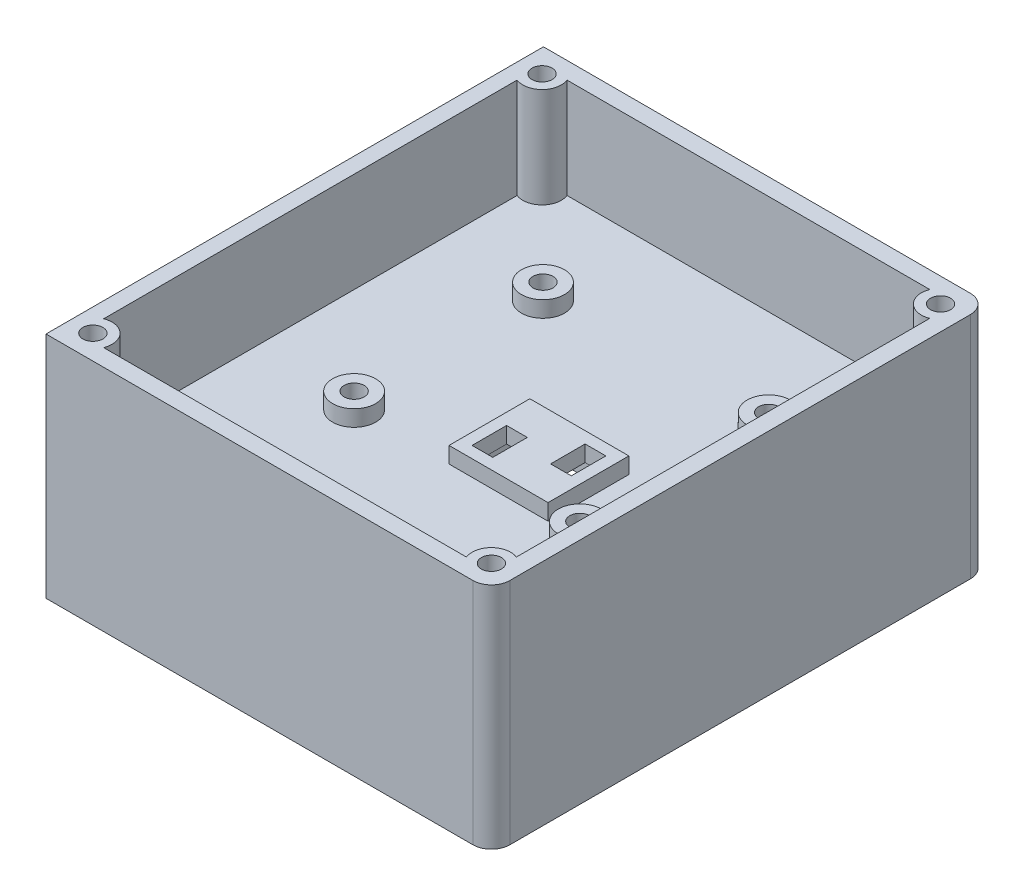
SolidWorks part; units mm, degrees
ref_plane "Front Plane" through (0, 0, 0) normal (0, 0, 1) x (1, 0, 0)
ref_plane "Top Plane" through (0, 0, 0) normal (0, 1, 0) x (1, 0, 0)
ref_plane "Right Plane" through (0, 0, 0) normal (1, 0, 0) x (0, 0, -1)
sketch "Sketch1" plane through (0, 0, 0) normal (0, 1, 0) x (1, 0, 0)
  line L1 (73.9904, 53.1) -> (166.6904, 53.1)
  line L2 (73.9904, 53.1) -> (73.9904, -54.9)
  line L3 (73.9904, -54.9) -> (166.6904, -54.9)
  line L4 (170.6904, 49.1) -> (170.6904, -50.9)
  line L6 (170.6904, -50.9) -> (170.6904, 49.1) construction
  line L7 (73.6904, 53.1) -> (73.6904, 45.1) construction
  line L8 (166.6904, 53.1) -> (73.6904, 53.1) construction
  line L9 (73.6904, -54.9) -> (166.6904, -54.9) construction
  line L10 (166.6904, -50.9) -> (166.6904, 49.1) construction
  line L11 (166.9904, 49.4) -> (77.3904, 49.4)
  line L12 (166.9904, 49.4) -> (166.9904, -51.2)
  line L13 (166.9904, -51.2) -> (77.3904, -51.2)
  line L14 (77.3904, 49.4) -> (77.3904, -51.2)
  line L15 (166.6904, 49.1) -> (77.6904, 49.1) construction
  line L16 (166.6904, 49.1) -> (77.6904, 49.1) construction
  line L17 (166.6904, -50.9) -> (166.6904, 49.1) construction
  arc A0 (166.6904, -54.9) -> (170.6904, -50.9) centre (166.6904, -50.9) ccw
  arc A1 (166.6904, 53.1) -> (170.6904, 49.1) centre (166.6904, 49.1) cw
  point P24 (122.1904, 49.1)
  point P25 (122.1904, 49.4)
  point P28 (166.6904, -0.9)
  point P29 (166.9904, -0.9)
  dimension "D4" = 4
  dimension "D1" = 0.3
  dimension "D2" = 0.3
  dimension "D3" = 0.3
extrude "Boss-Extrude1" add sketch "Sketch1" along normal up to surface (49.7 mm away)
sketch "Sketch4" plane through (77.3904, 0, 0) normal (1, 0, 0) x (0, 0, -1)
  line L0 (49.4, 0) -> (-51.2, 0) construction
  line L1 (28.8, 12) -> (45.4, 12)
  line L2 (28.8, 12) -> (28.8, 0)
  line L3 (28.8, 0) -> (45.4, 0)
  line L4 (45.4, 12) -> (45.4, 0)
  line L5 (29.1, 11.7) -> (29.1, -0.3) construction
  line L6 (29.1, 11.7) -> (45.1, 11.7) construction
  point P10 (37.1, 11.7)
  point P11 (37.1, 12)
  dimension "D1" = 0.3
  dimension "D2" = 0.3
extrude "Cut-Extrude1" cut sketch "Sketch4" against normal through all
sketch "Sketch5" plane through (77.3904, 0, 0) normal (1, 0, 0) x (0, 0, -1)
  line L0 (-51.2, 49.7) -> (-51.2, 0) construction
  line L1 (-51.2, 25) -> (49.4, 25)
  line L2 (-51.2, 25) -> (-51.2, 28)
  line L3 (-51.2, 28) -> (49.4, 28)
  line L4 (49.4, 25) -> (49.4, 28)
  line L5 (49.4, 49.7) -> (49.4, 0) construction
  line L6 (45.1, 24.7) -> (-46.9, 24.7) construction
  dimension "D1" = 3
  dimension "D2" = 0.3
extrude "Boss-Extrude2" add sketch "Sketch5" along normal up to surface (89.6 mm away) up to face at (166.9904, 24.85, 0.9)
sketch "Sketch7" plane through (0, 28, 0) normal (0, 1, 0) x (1, 0, 0)
  line L0 (77.3904, 49.4) -> (78.9283, 47.862) construction
  line L1 (166.9904, 49.4) -> (77.3904, 49.4) construction
  line L2 (77.3904, -0.9) -> (166.9904, -0.9) construction
  line L3 (77.3904, 49.4) -> (77.3904, -51.2) construction
  line L4 (166.9904, -51.2) -> (166.9904, 49.4) construction
  line L5 (122.1904, -51.2) -> (122.1904, 49.4) construction
  line L6 (166.9904, -51.2) -> (77.3904, -51.2) construction
  line L7 (166.9904, 49.4) -> (165.4524, 47.862) construction
  line L8 (166.9904, -51.2) -> (165.4524, -49.662) construction
  line L9 (77.3904, -51.2) -> (78.9283, -49.662) construction
  circle A0 centre (78.9283, 47.862) radius 2.175
  circle A1 centre (78.9283, 47.862) radius 4.175
  circle A2 centre (165.4524, 47.862) radius 4.175
  circle A3 centre (165.4524, 47.862) radius 2.175
  circle A4 centre (165.4524, -49.662) radius 2.175
  circle A5 centre (165.4524, -49.662) radius 4.175
  circle A6 centre (78.9283, -49.662) radius 4.175
  circle A7 centre (78.9283, -49.662) radius 2.175
  dimension "D1" = 4.35
  dimension "D2" = 2
  dimension "D3" = 45
extrude "Boss-Extrude3" add sketch "Sketch7" along normal up to surface (21.7 mm away) contours A6 | A1 | A2 | A5 up to face at (122.1904, 49.7, 0.9)
extrude "Cut-Extrude2" cut sketch "Sketch7<3>" against normal blind 5 from surface contours A0 | A3 | A4 | A7 starting at face at (122.1904, 49.7, 0.9)
sketch "Sketch7<3>" plane through (0, 28, 0) normal (0, 1, 0) x (1, 0, 0) same geometry as "Sketch7"
sketch "Sketch9" plane through (0, 28, 0) normal (0, 1, 0) x (1, 0, 0)
  line L0 (166.9904, -45.7806) -> (166.9904, 43.9806) construction
  line L1 (161.571, 49.4) -> (82.8097, 49.4) construction
  circle A0 centre (99.9904, 27) radius 2.175
  circle A1 centre (148.9904, 27) radius 2.175
  circle A2 centre (99.9904, -14) radius 2.175
  circle A3 centre (148.9904, -14) radius 2.175
  circle A4 centre (148.9904, -14) radius 4.675
  circle A5 centre (99.9904, -14) radius 4.675
  circle A6 centre (99.9904, 27) radius 4.675
  circle A7 centre (148.9904, 27) radius 4.675
  dimension "D1" = 4.35
  dimension "D2" = 2.5
  dimension "D4" = 22.4
  dimension "D3" = 18
  dimension "D5" = 49
  dimension "D6" = 41
extrude "Boss-Extrude4" add sketch "Sketch9" along normal blind 3.5
extrude "Cut-Extrude4" cut sketch "Sketch9<2>" against normal blind 1.5 contours A0 | A1 | A3 | A2
sketch "Sketch9<2>" plane through (0, 28, 0) normal (0, 1, 0) x (1, 0, 0) same geometry as "Sketch9"
sketch "Sketch11" plane through (0, 28, 0) normal (0, 1, 0) x (1, 0, 0)
  line L1 (127.4904, -3.9) -> (122.9904, -3.9)
  line L2 (127.4904, -3.9) -> (127.4904, -11.4)
  line L3 (127.4904, -11.4) -> (122.9904, -11.4)
  line L4 (122.9904, -3.9) -> (122.9904, -11.4)
  line L5 (134.9904, -6.35) -> (139.4904, -6.35)
  line L6 (134.9904, -6.35) -> (134.9904, 1.15)
  line L7 (134.9904, 1.15) -> (139.4904, 1.15)
  line L8 (139.4904, -6.35) -> (139.4904, 1.15)
  line L9 (120.4904, -13.9) -> (141.9904, -13.9)
  line L10 (120.4904, -13.9) -> (120.4904, 3.65)
  line L11 (120.4904, 3.65) -> (141.9904, 3.65)
  line L12 (141.9904, -13.9) -> (141.9904, 3.65)
  circle A0 centre (148.9904, -14) radius 2.175 construction
  circle A2 centre (148.9904, -14) radius 2.175 construction
  dimension "D1" = 7.5
  dimension "D2" = 4.5
  dimension "D3" = 2.45
  dimension "D4" = 7.5
  dimension "D5" = 2.5
  dimension "D6" = 2.5
  dimension "D7" = 2.5
  dimension "D8" = 2.5
  dimension "D9" = 21.5
  dimension "D10" = 17.55
  dimension "D11" = 7
  dimension "D12" = 0.1
extrude "Boss-Extrude5" add sketch "Sketch11" along normal up to surface (3.5 mm away) up to face at (148.9904, 31.5, 18.675)
sketch "Sketch12" plane through (0, 25, 0) normal (0, -1, 0) x (1, 0, 0)
  line L0 (122.9904, 11.4) -> (127.4904, 11.4) construction
  line L1 (122.7404, 11.65) -> (139.7404, 11.65)
  line L2 (122.7404, 11.65) -> (122.7404, -1.4)
  line L3 (122.7404, -1.4) -> (139.7404, -1.4)
  line L4 (139.7404, 11.65) -> (139.7404, -1.4)
  line L5 (122.9904, 3.9) -> (122.9904, 11.4) construction
  line L6 (139.4904, 6.35) -> (139.4904, -1.15) construction
  line L7 (139.4904, -1.15) -> (134.9904, -1.15) construction
  dimension "D1" = 0.25
  dimension "D2" = 0.25
  dimension "D3" = 0.25
  dimension "D4" = 0.25
extrude "Cut-Extrude5" cut sketch "Sketch12" against normal blind 3
equation "\"D6@Sketch11\"=\"D5@Sketch11\""
equation "\"D8@Sketch11\"=\"D7@Sketch11\""
